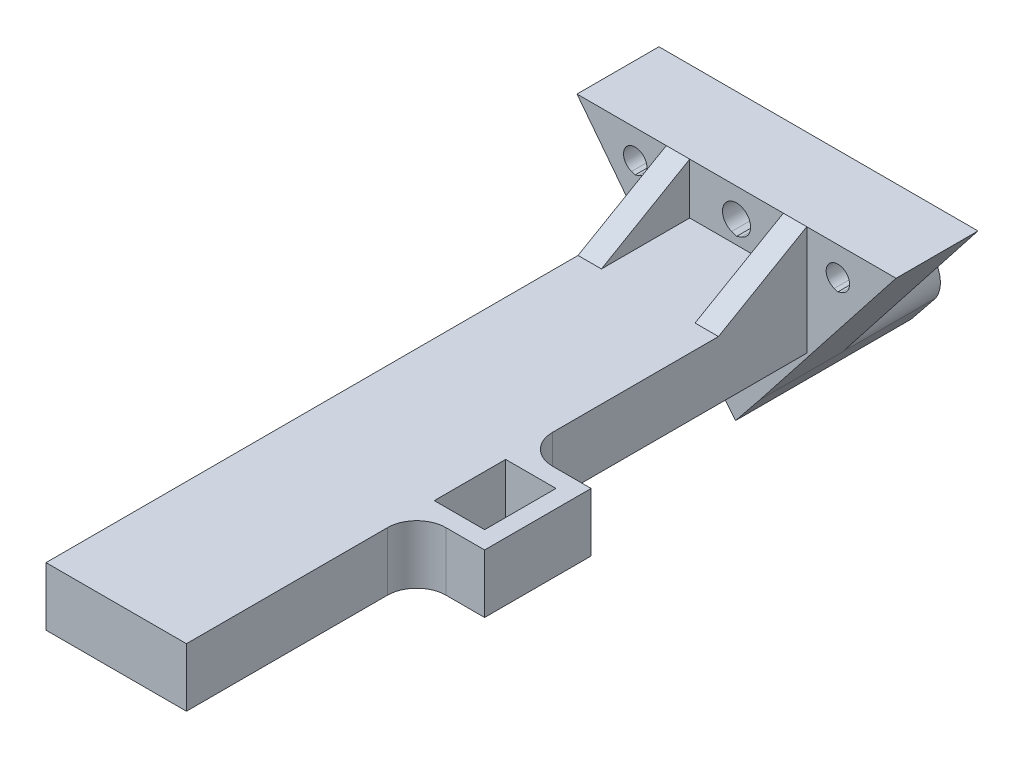
SolidWorks part; units mm, degrees
note: The reader was unsure of these and kept them because the rebuilt part matched: shared geometry of "Sketch5<3>".
ref_plane "Front Plane" through (0, 0, 0) normal (0, 0, 1) x (1, 0, 0)
ref_plane "Top Plane" through (0, 0, 0) normal (0, 1, 0) x (1, 0, 0)
ref_plane "Right Plane" through (0, 0, 0) normal (1, 0, 0) x (0, 0, -1)
sketch "Sketch1" plane through (0, 0, 0) normal (0, 1, 0) x (1, 0, 0)
  line L0 (-1.342, 19.5385) -> (-1.342, -40.4615) construction
  line L1 (-7.342, 19.5385) -> (4.658, 19.5385)
  line L2 (-7.342, 19.5385) -> (-7.342, -40.4615)
  line L3 (-7.342, -40.4615) -> (4.658, -40.4615)
  line L4 (4.658, 19.5385) -> (4.658, -40.4615)
  line L8 (-7.342, -10.4615) -> (4.658, -10.4615) construction
  dimension "D1" = 12
  dimension "D2" = 60
extrude "Boss-Extrude1" add sketch "Sketch1" along normal blind 1 contours L1 L4 L3 L2
sketch "Sketch4" plane through (0, 0, 0) normal (0, 1, 0) x (1, 0, 0)
  line L0 (-5.6775, -38.4615) -> (2.9083, -38.4615)
  line L1 (-6.3838, 2.2418) -> (-6.3846, 2.241)
  line L3 (3.6154, -37.7544) -> (3.6154, -29.1686)
  line L5 (-6.3846, 2.2426) -> (-6.3846, 2.241)
  line L6 (-5.6773, -28.4612) -> (-1.3898, -32.7493)
  line L7 (-2.0914, -3.461) -> (-6.3846, -7.7539)
  line L8 (-6.3846, -37.7544) -> (-6.3846, -29.1686)
  line L9 (-0.6778, -3.462) -> (3.6154, -7.755)
  line L10 (-6.3846, -27.7544) -> (-6.3846, -19.1681)
  line L11 (-6.3846, -17.7422) -> (-6.3846, -9.1682)
  line L12 (-1.3872, -12.7512) -> (2.9085, -8.461)
  line L13 (-2.0914, -3.461) -> (-6.3846, 0.8321)
  line L14 (-0.6783, 6.5389) -> (3.6154, 10.8326)
  line L15 (2.9129, 11.5385) -> (-5.6778, 11.5385)
  line L16 (3.6154, -27.7539) -> (3.6154, -19.1685)
  line L17 (-2.0915, -23.4612) -> (-6.3846, -19.1681)
  line L18 (-6.3846, -7.7539) -> (-6.3846, 0.8321)
  line L19 (3.6154, -7.755) -> (3.6154, 0.8312)
  line L20 (-6.3846, 2.2426) -> (-6.3846, 10.831)
  line L21 (-6.3846, -37.7544) -> (-2.0961, -33.4571)
  line L22 (-5.6775, -38.4615) -> (-1.3846, -34.1686)
  line L23 (2.9083, -38.4615) -> (-1.3846, -34.1686)
  line L24 (3.6154, -37.7544) -> (-0.7492, -33.5332)
  line L25 (-6.3846, -27.7544) -> (-2.0915, -23.4612)
  line L26 (-5.6773, -28.4612) -> (-1.3846, -24.1681)
  line L27 (2.899, -28.4517) -> (-1.3846, -24.1681)
  line L28 (-0.6773, -23.4612) -> (3.6154, -27.7539)
  line L29 (-6.3846, -17.7422) -> (-2.0948, -13.4579)
  line L30 (-5.677, -18.4616) -> (-1.3846, -14.1681)
  line L31 (2.9084, -18.4612) -> (-1.3846, -14.1681)
  line L32 (-0.6769, -13.4615) -> (3.6154, -17.7543)
  line L33 (-5.677, -8.4612) -> (-1.3846, -4.1678)
  line L35 (2.9085, -8.461) -> (-1.3846, -4.1678)
  line L36 (-0.6783, 6.5389) -> (3.6154, 2.2454)
  line L37 (-6.3838, 2.2418) -> (-2.0896, 6.536)
  line L38 (-5.6795, 1.5377) -> (-1.3854, 5.8318)
  line L39 (2.9082, 1.5382) -> (-1.3854, 5.8318)
  line L41 (-2.0961, -33.4571) -> (-6.3846, -29.1686)
  line L42 (-1.3844, -22.7541) -> (2.9084, -18.4612)
  line L43 (-0.7492, -33.5332) -> (3.6154, -29.1686)
  line L44 (3.6154, -17.7543) -> (3.6154, -9.1692)
  line L45 (-1.3898, -32.7493) -> (2.899, -28.4517)
  line L46 (-5.6778, 11.5385) -> (-1.3825, 7.2431)
  line L47 (-0.6769, -13.4615) -> (3.6154, -9.1692)
  line L48 (-1.3844, -22.7541) -> (-5.677, -18.4616)
  line L49 (-0.6773, -23.4612) -> (3.6154, -19.1685)
  line L52 (-2.0948, -13.4579) -> (-6.3846, -9.1682)
  line L53 (2.9082, 1.5382) -> (-1.3852, -2.7549)
  line L55 (-1.3872, -12.7512) -> (-5.677, -8.4612)
  line L56 (-0.6778, -3.462) -> (3.6154, 0.8312)
  line L58 (3.6154, 2.2454) -> (3.6154, 10.8326)
  line L61 (-1.3852, -2.7549) -> (-5.6795, 1.5377)
  line L66 (-1.3825, 7.2431) -> (2.9129, 11.5385)
  line L67 (-2.0896, 6.536) -> (-6.3846, 10.831)
extrude "Boss-Extrude5" add sketch "Sketch4" against normal blind 4
sketch "Sketch3" plane through (0, -4, 0) normal (0, -1, 0) x (1, 0, 0)
  line L0 (-1.342, 40.4615) -> (-1.342, -19.5385) construction
  line L1 (-7.342, 40.4615) -> (4.658, 40.4615) construction
  line L2 (-7.342, -19.5385) -> (4.658, -19.5385) construction
  line L3 (4.658, 10.4615) -> (-7.342, 10.4615) construction
  line L4 (4.658, -19.5385) -> (4.658, 40.4615) construction
  line L5 (-7.342, -19.5385) -> (-7.342, 40.4615) construction
  line L6 (3.658, 36.4615) -> (3.658, -9.9392)
  line L7 (-6.3846, 36.4615) -> (-6.3846, -9.9392)
  line L8 (-5.9846, 36.4615) -> (-6.3846, 36.4615)
  line L9 (3.658, 36.4615) -> (3.2154, 36.4615)
  line L10 (-5.9846, 36.4615) -> (-5.9846, -9.9392)
  line L11 (3.2154, 36.4615) -> (3.2154, -9.9392)
  line L13 (-5.6775, 38.4615) -> (2.9083, 38.4615) construction
  line L14 (3.658, -9.9392) -> (3.2154, -9.9392)
  line L15 (-5.9846, -9.9392) -> (-6.3846, -9.9392)
  dimension "D1" = 5
  dimension "D3" = 0.4
  dimension "D4" = 2
extrude "Cut-Extrude1" cut sketch "Sketch3" against normal blind 3
sketch "Sketch5" plane through (0, 0, -19.5385) normal (0, 0, -1) x (-1, 0, 0)
  line L0 (1.342, -4) -> (1.342, 17.9458) construction
  line L1 (7.342, -4) -> (-4.658, -4) construction
  line L2 (-4.658, 1) -> (-4.658, -4) construction
  line L3 (-4.658, -1.5) -> (7.342, -1.5) construction
  line L4 (-4.658, 1) -> (-4.658, -4) construction
  line L5 (7.342, 1) -> (7.342, -4) construction
  line L6 (-4.658, 1) -> (8.3846, 1)
  line L7 (-12.2888, 5.3559) -> (14.9728, 5.3559)
  line L8 (9.6927, 1.9661) -> (9.9994, 1.8577)
  line L9 (-7.6221, 1.9661) -> (-7.3154, 1.8577)
  line L10 (3.5374, -9.4159) -> (14.9728, 5.3559)
  line L11 (-12.2888, 5.3559) -> (-0.6898, -9.4092)
  line L12 (7.342, 1) -> (-4.658, 1) construction
  line L13 (-7.0087, 1.9661) -> (-7.3154, 1.8577)
  line L14 (1.342, 2.9179) -> (16.7595, 2.9179) construction
  line L15 (-0.6898, -9.4092) -> (1.4259, -12.0334)
  line L16 (10.3062, 1.9661) -> (9.9994, 1.8577)
  line L17 (3.5374, -9.4159) -> (1.4259, -12.0334)
  line L18 (0.9215, 1.794) -> (1.342, 1.6367)
  line L19 (1.342, 1.6367) -> (1.7626, 1.794)
  arc A0 (1.7626, 1.794) -> (0.9215, 1.794) centre (1.342, 2.9179) ccw
  arc A1 (10.3062, 1.9661) -> (9.6927, 1.9661) centre (9.9994, 2.9179) ccw
  arc A2 (-7.6221, 1.9661) -> (-7.0087, 1.9661) centre (-7.3154, 2.9179) cw
  arc A3 (3.5374, -9.4159) -> (-0.6898, -9.4092) centre (1.4259, -8.0773) ccw
  dimension "D1" = 2.4
  dimension "D2" = 2
  dimension "D5" = 5
extrude "Boss-Extrude6" add sketch "Sketch5" against normal blind 7
extrude "Boss-Extrude11" add sketch "Sketch5<3>" along normal blind 8 contours L17 A3 L15
sketch "Sketch5<3>" plane through (0, 0, -19.5385) normal (0, 0, -1) x (-1, 0, 0) same geometry as "Sketch5"
sketch "Sketch11" plane through (-7.342, 0, 0) normal (-1, 0, 0) x (0, 0, 1)
  line L0 (-12.5385, 5.3559) -> (-4.9938, 1)
  line L3 (-12.5385, 1) -> (40.4615, 1) construction
  line L4 (-4.9938, 1) -> (-12.5385, 1)
  line L5 (-12.5385, -9.4159) -> (-12.5385, 5.3559) construction
  line L6 (-12.5385, 1) -> (-12.5385, 5.3559)
  dimension "D1" = 60
extrude "Boss-Extrude12" add sketch "Sketch11" against normal blind 2
ref_plane "Plane1" through (-1.342, 0, 0) normal (-1, 0, 0) x (0, 0, 1)
sketch "Sketch12" plane through (-1.342, 0, 0) normal (-1, 0, 0) x (0, 0, 1)
  line L0 (-13.8591, -4.4186) -> (-13.8591, -9.6832)
  line L1 (-13.8591, -9.6832) -> (-6.411, -3.8889)
  line L2 (-6.411, -3.8889) -> (-6.411, 0.3167)
  line L3 (-6.411, 0.3167) -> (-13.8591, 0.3167)
  line L4 (-13.8591, 0.3167) -> (-13.8591, -4.4186)
  line L5 (-13.8591, -4.4186) -> (-12.4258, -4.4186)
extrude "Boss-Extrude13" add sketch "Sketch12" along normal mid plane 1.5
sketch "Sketch14" plane through (4.658, 0, 0) normal (1, 0, 0) x (0, 0, -1)
  line L0 (4.9938, 1) -> (12.5385, 5.3559)
  line L1 (12.5385, 5.3559) -> (12.5385, 1)
  line L2 (12.5385, 5.3559) -> (12.5385, -9.4092) construction
  line L3 (12.5385, 5.3559) -> (12.5385, 1) construction
  line L4 (12.5385, 1) -> (4.9938, 1)
extrude "Boss-Extrude15" add sketch "Sketch14" against normal blind 2
sketch "Sketch15" plane through (0, 1, 0) normal (0, 1, 0) x (1, 0, 0)
  line L0 (4.658, 4.9938) -> (4.658, -40.4615) construction
  line L1 (4.658, -13.1875) -> (8.958, -13.1875)
  line L2 (4.658, -13.1875) -> (4.658, -19.2875)
  line L3 (4.658, -19.2875) -> (8.958, -19.2875)
  line L4 (8.958, -13.1875) -> (8.958, -19.2875)
  line L5 (4.658, -11.6875) -> (10.458, -11.6875)
  line L6 (10.458, -11.6875) -> (10.458, -20.7875)
  line L7 (10.458, -20.7875) -> (4.658, -20.7875)
  line M8 (4.658, -40.4615) -> (4.658, 4.9938)
  dimension "D1" = 6.1
  dimension "D2" = 4.3
  dimension "D3" = 1.5
  dimension "D4" = 1.5
  dimension "D5" = 1.5
extrude "Boss-Extrude16" add sketch "Sketch15" against normal blind 5 contours L7 L6 L5 L1 L4 L3 M8
fillet "Fillet1" radius 2.5 1 edges at (4.658, -1.5, 20.7875)
fillet "Fillet2" radius 2.5 1 edges at (4.658, -1.5, 11.6875)
